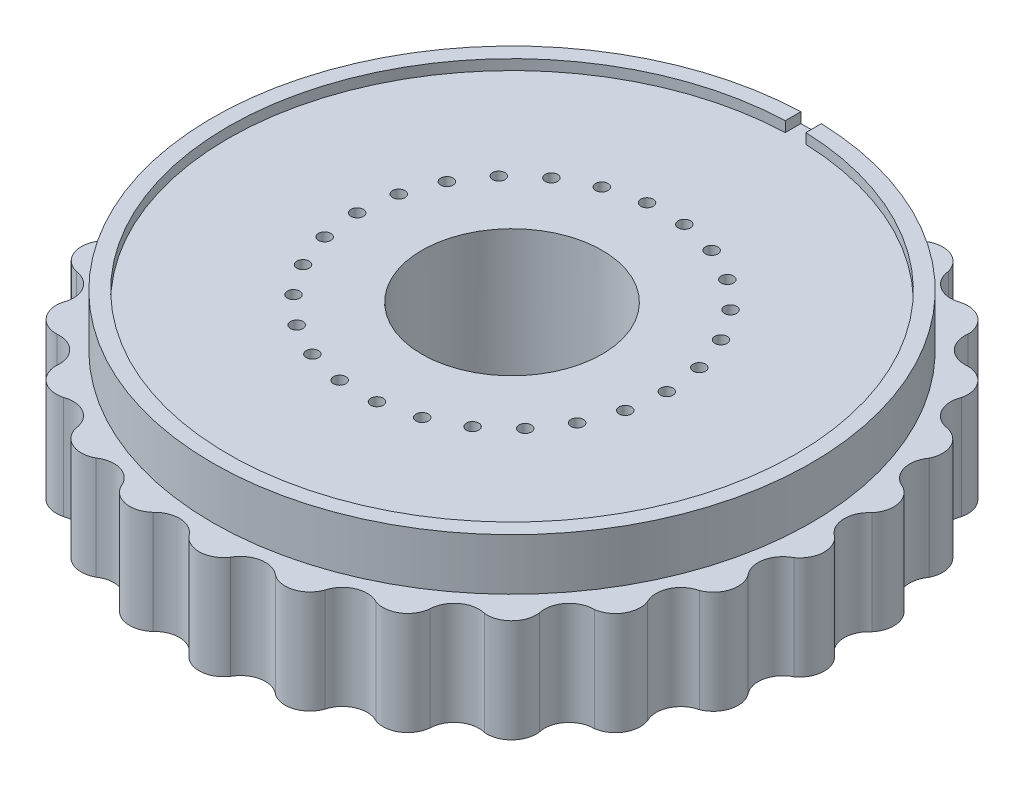
SolidWorks part; units mm, degrees
material "1060 Alloy"
ref_plane "Front Plane" through (0, 0, 0) normal (0, 0, 1) x (1, 0, 0)
ref_plane "Top Plane" through (0, 0, 0) normal (0, 1, 0) x (1, 0, 0)
ref_plane "Right Plane" through (0, 0, 0) normal (1, 0, 0) x (0, 0, -1)
sketch "Wheel" plane through (0, 0, 0) normal (0, 1, 0) x (1, 0, 0)
  line L0 (0, 0) -> (45.5848, 0) construction
  line L1 (0, 0) -> (41.8043, 10.3038) construction
  line L2 (0, 0) -> (29.1283, 7.1795)
  line L3 (0, 0) -> (30, 0)
  line L4 (0, 0) -> (42.9769, 5.2183) construction
  line L5 (29.1283, 7.1795) -> (30.3419, 7.4786)
  line L6 (30, 0) -> (31.25, 0)
  circle A0 centre (0, 0) radius 30 construction
  circle A1 centre (0, 0) radius 32.5 construction
  circle A2 centre (0, 0) radius 31.25 construction
  arc A3 (30.3419, 7.4786) -> (31.0877, 3.7747) centre (29.2636, 5.3345) cw
  arc A4 (31.0877, 3.7747) -> (31.25, 0) centre (0.4989, 0.5684) ccw construction
  arc A5 (31.0877, 3.7747) -> (31.25, 0) centre (32.6478, 1.951) ccw
  circle A6 centre (32.6478, 1.951) radius 2.4 construction
  dimension "D1" = 60
  dimension "D2" = 2.5
  dimension "D4" = 1.25
  dimension "D5" = 6.923
  dimension "D6" = 4.8
  dimension "D3" = 13.846
extrude "Extrude wheel" add sketch "Wheel" along normal blind 10
pattern_circular "CirPattern1" count 26 over 360 about axis through (0, 10, 0) along (0, -1, 0) of "Extrude wheel" reverse direction yes
sketch "Sketch4" plane through (0, 10, 0) normal (0, 1, 0) x (1, 0, 0)
  circle A0 centre (0, 0) radius 29
  dimension "D1" = 58
extrude "Boss-Extrude1" add sketch "Sketch4" along normal blind 5
sketch "Bearing hole" plane through (0, 15, 0) normal (0, 1, 0) x (1, 0, 0)
  circle A0 centre (0, 0) radius 8.7313
  dimension "D1" = 17.4625
extrude "Cut bearing hole" cut sketch "Bearing hole" against normal through all
sketch "PCB inset" plane through (0, 15, 0) normal (0, 1, 0) x (1, 0, 0)
  line L0 (-1, 27.4818) -> (-1, 29.4818)
  line L1 (-1, 29.4818) -> (1, 29.4818)
  line L2 (1, 29.4818) -> (1, 27.4818)
  line L3 (0, 0) -> (0, 37.4364) construction
  arc A0 (-1, 27.4818) -> (1, 27.4818) centre (0, 0) ccw
  point P7 (0, 29.4818)
  dimension "D1" = 55
  dimension "D3" = 2
  dimension "D2" = 2
extrude "PCB inset cut" cut sketch "PCB inset" against normal blind 1
sketch "PCB inset 2" plane through (0, 0, 0) normal (0, -1, 0) x (1, 0, 0)
  line L0 (0, 0) -> (0, -38.2083) construction
  line L1 (1, -27.4818) -> (1, -29.4818)
  line L2 (1, -29.4818) -> (-1, -29.4818)
  line L3 (-1, -29.4818) -> (-1, -27.4818)
  arc A0 (1, -27.4818) -> (-1, -27.4818) centre (0, 0) ccw
  point P8 (0, -29.4818)
  dimension "D1" = 55
  dimension "D2" = 2
  dimension "D3" = 2
extrude "PCB inset cut 2" cut sketch "PCB inset 2" against normal blind 1
sketch "PCB output holes" plane through (0, 14, 0) normal (0, 1, 0) x (1, 0, 0)
  line L0 (0, 0) -> (60.8892, 0) construction
  line L1 (0, 0) -> (59.1575, 14.581) construction
  line L2 (0, 0) -> (60.8984, 0) construction
  circle A0 centre (15, 0) radius 0.6
  circle A1 centre (14.5641, -3.5897) radius 0.6
  circle A2 centre (13.2818, -6.9708) radius 0.6
  circle A3 centre (11.2277, -9.9468) radius 0.6
  circle A4 centre (8.521, -12.3448) radius 0.6
  circle A5 centre (5.3191, -14.0252) radius 0.6
  circle A6 centre (1.8081, -14.8906) radius 0.6
  circle A7 centre (-1.8081, -14.8906) radius 0.6
  circle A8 centre (-5.3191, -14.0252) radius 0.6
  circle A9 centre (-8.521, -12.3448) radius 0.6
  circle A10 centre (-11.2277, -9.9468) radius 0.6
  circle A11 centre (-13.2818, -6.9708) radius 0.6
  circle A12 centre (-14.5641, -3.5897) radius 0.6
  circle A13 centre (-15, 0) radius 0.6
  circle A14 centre (-14.5641, 3.5897) radius 0.6
  circle A15 centre (-13.2818, 6.9708) radius 0.6
  circle A16 centre (-11.2277, 9.9468) radius 0.6
  circle A17 centre (-8.521, 12.3448) radius 0.6
  circle A18 centre (-5.3191, 14.0252) radius 0.6
  circle A19 centre (-1.8081, 14.8906) radius 0.6
  circle A20 centre (1.8081, 14.8906) radius 0.6
  circle A21 centre (5.3191, 14.0252) radius 0.6
  circle A22 centre (8.521, 12.3448) radius 0.6
  circle A23 centre (11.2277, 9.9468) radius 0.6
  circle A24 centre (13.2818, 6.9708) radius 0.6
  circle A25 centre (14.5641, 3.5897) radius 0.6
  point P60 (0, 0)
  dimension "D5" = 1.2
  dimension "D1" = 13.846
  dimension "D2" = 0
  dimension "D3" = 15
  dimension "D4" = 26
extrude "PCB output holes cut" cut sketch "PCB output holes" against normal through all
equation "\"Diameter\"=60"
equation "\"D1@Wheel\"=\"Diameter\""
equation "\"D5@Wheel\"=360/26/2"
equation "\"Bearing size\"= 17.4625mm"
equation "\"D1@Bearing hole\"=\"Bearing size\""
equation "\"PCB diameter\"= 55mm"
equation "\"D1@PCB inset\"=\"PCB diameter\""
equation "\"D1@PCB inset 2\"=\"PCB diameter\""
